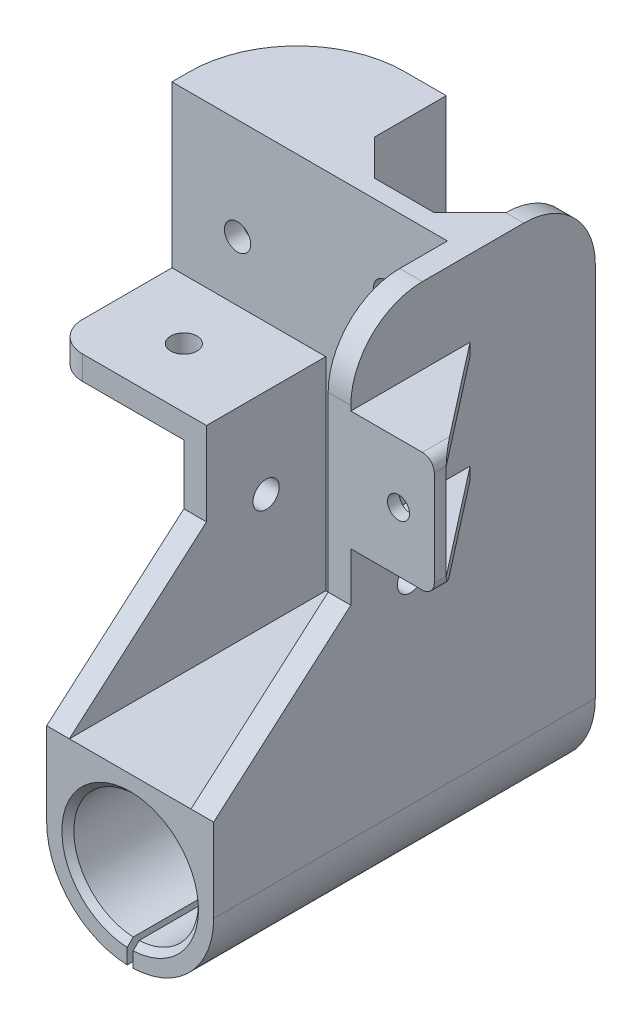
SolidWorks part; units mm, degrees
material "ABS"
ref_plane "Front Plane" through (0, 0, 0) normal (0, 0, 1) x (1, 0, 0)
ref_plane "Top Plane" through (0, 0, 0) normal (0, 1, 0) x (1, 0, 0)
ref_plane "Right Plane" through (0, 0, 0) normal (1, 0, 0) x (0, 0, -1)
sketch "Sketch1" plane through (0, 0, 0) normal (0, 0, 1) x (1, 0, 0)
  line L0 (-14, 0) -> (-14, 44)
  line L1 (-14, 44) -> (-36, 44)
  line L2 (-36, 44) -> (-36, 75)
  line L3 (-36, 75) -> (14, 75)
  line L4 (14, 75) -> (14, 0)
  arc A0 (-14, 0) -> (14, 0) centre (0, 0) ccw
  dimension "D3" = 28
  dimension "D1" = 31
  dimension "D2" = 22
  dimension "D4" = 75
extrude "Boss-Extrude1" add sketch "Sketch1" along normal blind 64
sketch "Sketch2" plane through (0, 75, 0) normal (0, 1, 0) x (1, 0, 0)
  line L0 (-11, 0) -> (-11, -12)
  line L1 (14, 0) -> (-36, 0) construction
  line L2 (-11, -12) -> (-5, -18)
  line L3 (-5, -18) -> (5, -18)
  line L4 (5, -18) -> (11, -12)
  line L5 (11, -12) -> (11, 0)
  line L6 (11, 0) -> (-11, 0)
  line L7 (14, -64) -> (14, 0) construction
  dimension "D1" = 10
  dimension "D2" = 22
  dimension "D3" = 3
  dimension "D4" = 12
  dimension "D5" = 18
extrude "Cut-Extrude1" cut sketch "Sketch2" against normal blind 61
sketch "Sketch3" plane through (14, 0, 0) normal (1, 0, 0) x (0, 0, -1)
  line L0 (-64, 14) -> (-41, 34)
  line L1 (-64, 0) -> (-64, 75) construction
  line L2 (-41, 34) -> (-41, 75)
  line L3 (-64, 75) -> (0, 75) construction
  line L4 (-41, 75) -> (-64, 75)
  line L5 (-64, 75) -> (-64, 14)
  dimension "D1" = 23
  dimension "D2" = 41
  dimension "D3" = 61
extrude "Cut-Extrude2" cut sketch "Sketch3" against normal through all
sketch "Sketch4" plane through (0, 0, 64) normal (0, 0, 1) x (1, 0, 0)
  line L0 (-10.2, 14) -> (-10.2, 48)
  line L1 (-14, 14) -> (14, 14) construction
  line L2 (-10.2, 48) -> (-36, 48)
  line L3 (-36, 44) -> (-36, 75) construction
  line L4 (-36, 48) -> (-36, 75)
  line L5 (-36, 75) -> (10.2, 75)
  line L6 (-36, 75) -> (14, 75) construction
  line L7 (10.2, 75) -> (10.2, 14)
  line L8 (10.2, 14) -> (-10.2, 14)
  line L9 (-14, 14) -> (-14, 34) construction
  line L10 (14, 14) -> (14, 34) construction
  line L11 (-14, 44) -> (-36, 44) construction
  dimension "D1" = 3.8
  dimension "D2" = 3.8
  dimension "D3" = 4
extrude "Cut-Extrude3" cut sketch "Sketch4" against normal blind 43
sketch "Sketch5" plane through (0, 0, 64) normal (0, 0, 1) x (1, 0, 0)
  line L0 (0, -10.45) -> (0, -14) construction
  line L1 (-0.5, -10.438) -> (-0.5, -13.9911)
  line L2 (0.5, -10.438) -> (0.5, -13.9911)
  line L3 (-0.5, -10.45) -> (-0.5, -17.5466) construction
  line L4 (0, -10.45) -> (0, -17.5466) construction
  line L5 (0.5, -10.45) -> (0.5, -17.5466) construction
  arc A0 (0.5, -10.438) -> (-0.5, -10.438) centre (0, 0) ccw
  arc A1 (-14, 0) -> (14, 0) centre (0, 0) ccw construction
  arc A2 (-0.5, -13.9911) -> (0.5, -13.9911) centre (0, 0) ccw
  dimension "D1" = 20.9
  dimension "D2" = 0.5
  dimension "D3" = 0.5
extrude "Cut-Extrude4" cut sketch "Sketch5" against normal through all
chamfer "Chamfer1" distance 1 angle 45 2 edges at (0, 10.45, 0) (0, 10.45, 64)
sketch "Sketch6" plane through (0, 0, 21) normal (0, 0, 1) x (1, 0, 0)
  line L0 (0, 14) -> (0, 27) construction
  line L1 (-10.2, 14) -> (10.2, 14) construction
  line L2 (-36, 48) -> (-10.2, 48) construction
  line L3 (-36, 75) -> (-36, 48) construction
  circle A0 centre (-25, 58) radius 2.2
  circle A1 centre (0, 62) radius 2.2
  circle A2 centre (0, 27) radius 2.2
  dimension "D1" = 4.4
  dimension "D2" = 35
  dimension "D4" = 10
  dimension "D5" = 11
  dimension "D3" = 13
extrude "Cut-Extrude5" cut sketch "Sketch6" against normal through all
sketch "Sketch7" plane through (14, 0, 0) normal (1, 0, 0) x (0, 0, -1)
  line L0 (-41, 62.2) -> (-21, 62.2)
  line L1 (-41, 34) -> (-41, 75) construction
  line L2 (-21, 62.2) -> (-21, 60.2)
  line L3 (-21, 60.2) -> (-39, 60.2)
  line L4 (-39, 60.2) -> (-39, 44.2)
  line L5 (-39, 44.2) -> (-21, 44.2)
  line L6 (-21, 44.2) -> (-21, 42.2)
  line L7 (-21, 42.2) -> (-41, 42.2)
  line L8 (-41, 42.2) -> (-41, 62.2)
  line L9 (-41, 75) -> (0, 75) construction
  dimension "D1" = 20
  dimension "D2" = 12.8
  dimension "D3" = 2
  dimension "D4" = 2
extrude "Boss-Extrude2" add sketch "Sketch7" along normal blind 14
sketch "Sketch8" plane through (0, 62.2, 0) normal (0, 1, 0) x (1, 0, 0)
  line L0 (14, -21) -> (28, -39)
  line L1 (28, -21) -> (28, -41) construction
  line L2 (28, -39) -> (28, -21)
  line L3 (28, -21) -> (14, -21)
  line L4 (28, -41) -> (14, -41) construction
  dimension "D1" = 2
extrude "Cut-Extrude6" cut sketch "Sketch8" against normal through all
sketch "Sketch9" plane through (0, 0, 41) normal (0, 0, 1) x (1, 0, 0)
  line L0 (22, 52.2) -> (28, 52.2) construction
  line L1 (28, 62.2) -> (28, 42.2) construction
  circle A0 centre (22, 52.2) radius 1.85
  dimension "D1" = 3.7
  dimension "D2" = 6
extrude "Cut-Extrude7" cut sketch "Sketch9" against normal through all
fillet "Fillet1" radius 2 2 edges at (28, 42.2, 40) (28, 62.2, 40)
fillet "Fillet2" radius 12 2 edges at (12.5, 75, 0) (12.1, 75, 41)
sketch "Sketch10" plane through (14, 0, 0) normal (1, 0, 0) x (0, 0, -1)
  line L0 (0, 0) -> (0, 63) construction
  line L1 (-29, 75) -> (-12, 75) construction
  circle A0 centre (-31, 33) radius 2.2
  dimension "D1" = 4.4
  dimension "D2" = 31
  dimension "D3" = 42
extrude "Cut-Extrude8" cut sketch "Sketch10" against normal through all
fillet "Fillet3" radius 5 1 edges at (-36, 46, 41)
fillet "Fillet4" radius 18 1 edges at (-36, 59.5, 0)
sketch "Sketch11" plane through (0, 48, 0) normal (0, 1, 0) x (1, 0, 0)
  line L0 (-36, -21) -> (-36, -36) construction
  line L1 (-10.2, -41) -> (-31, -41) construction
  circle A0 centre (-24, -31) radius 2.2
  dimension "D1" = 4.4
  dimension "D3" = 10
  dimension "D2" = 12
extrude "Cut-Extrude9" cut sketch "Sketch11" against normal through all
sketch "Sketch12" plane through (-36, 0, 0) normal (-1, 0, 0) x (0, 0, 1)
  line L0 (18, 75) -> (18, 44) construction
  line L1 (18, 71) -> (0, 71)
  line L2 (18, 71) -> (18, 48)
  line L3 (18, 48) -> (0, 48)
  line L4 (0, 71) -> (0, 48)
  line L5 (0, 44) -> (0, 75) construction
  line L6 (18, 75) -> (0, 75) construction
  line L7 (0, 44) -> (18, 44) construction
  dimension "D1" = 4
  dimension "D2" = 4
extrude "Cut-Extrude10" cut sketch "Sketch12" against normal blind 22
sketch "Sketch13" plane through (0, 44, 0) normal (0, -1, 0) x (1, 0, 0)
  circle A0 centre (-27, 9) radius 1.5
  circle A2 centre (-19, 9) radius 1.5
extrude "Cut-Extrude11" cut sketch "Sketch13" against normal up to next
